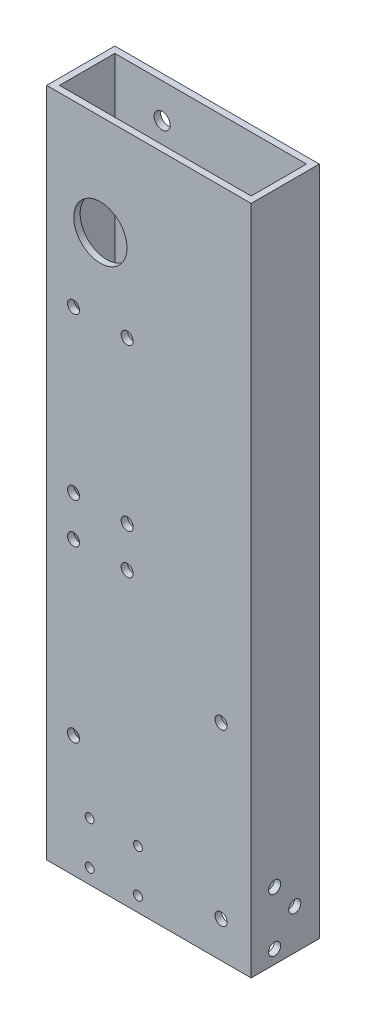
SolidWorks part; units mm, degrees
material "6063-T5"
ref_plane "Front Plane" through (0, 0, 0) normal (0, 0, 1) x (1, 0, 0)
ref_plane "Top Plane" through (0, 0, 0) normal (0, 1, 0) x (1, 0, 0)
ref_plane "Right Plane" through (0, 0, 0) normal (1, 0, 0) x (0, 0, -1)
sketch "Sketch1" plane through (0, 0, 0) normal (0, 1, 0) x (1, 0, 0)
  line L1 (-76.2, 25.4) -> (76.2, 25.4)
  line L2 (-76.2, 25.4) -> (-76.2, -25.4)
  line L3 (-76.2, -25.4) -> (76.2, -25.4)
  line L4 (76.2, 25.4) -> (76.2, -25.4)
  line L5 (-76.2, 25.4) -> (76.2, -25.4) construction
  line L6 (-76.2, -25.4) -> (76.2, 25.4) construction
  point P0 (0, 0)
  dimension "D1" = 152.4
  dimension "D2" = 50.8
extrude "Extrude-Thin1" add sketch "Sketch1" along normal blind 500 thin thin type one direction reverse wall 4.7625
hole_wizard "M8 Clearance Hole1" positions "Sketch3" profile "Sketch4" hole size "M8" standard "ANSI Metric" end condition through all
sketch "Sketch3" plane through (0, 0, 25.4) normal (0, 0, 1) x (1, 0, 0)
  line L0 (-76.2, 227) -> (3.8, 227)
  line L1 (-76.2, 500) -> (-76.2, 0) construction
  line L3 (-76.2, 0) -> (76.2, 0) construction
  line L4 (3.8, 227) -> (3.8, 387)
  line L5 (3.8, 387) -> (-76.2, 387)
  line L6 (-76.2, 387) -> (-76.2, 227)
  line L8 (-56.2, 217) -> (-16.2, 217)
  line L11 (-56.2, 217) -> (-56.2, 153.6667)
  line L12 (-56.2, 153.6667) -> (-56.2, 90.3333)
  line L13 (-56.2, 90.3333) -> (-56.2, 27)
  line L15 (-36.2, 217) -> (-36.2, 227)
  line L17 (-56.2, 27) -> (53.8, 27)
  line L18 (53.8, 27) -> (53.8, 153.6667)
  line L19 (53.8, 153.6667) -> (-56.2, 153.6667)
  line L22 (-56.2, 90.3333) -> (-76.2, 90.3333)
  line L27 (-36.2, 425) -> (-36.2, 387)
  circle A0 centre (-36.2, 425) radius 49.2125
  point P18 (-56.2, 217)
  point P19 (-16.2, 217)
  point P26 (-56.2, 90.3333)
  point P35 (53.8, 27)
  point P36 (53.8, 153.6667)
  dimension "D9" = 98.425
  dimension "D1" = 200
  dimension "D2" = 80
  dimension "D3" = 160
  dimension "D4" = 27
  dimension "D5" = 10
  dimension "D6" = 40
  dimension "D7" = 110
  dimension "D8" = 38
sketch "Sketch4" plane through (53.8, 153.6667, 25.4) normal (1, 0, 0) x (0, -1, 0)
  line L0 (0, 0) -> (0, 50.8)
  line L1 (0, 50.8) -> (4.5, 50.8)
  line L2 (4.5, 50.8) -> (4.5, 0)
  line L5 (4.5, 0) -> (0, 0)
  line L11 (0, -6.35) -> (0, 107.95) construction
  dimension "Thru Hole Dia." = 9
  dimension "Thru Hole Depth" = 50.8
hole_wizard "M8 Clearance Hole2" positions "Sketch5" profile "Sketch6" hole size "M8" standard "ANSI Metric" end condition through all
sketch "Sketch5" plane through (0, 0, 25.4) normal (0, 0, 1) x (1, 0, 0)
  line L1 (-56.2, 367) -> (-16.2, 367)
  line L2 (-56.2, 367) -> (-56.2, 247)
  line L3 (-56.2, 247) -> (-16.2, 247)
  line L4 (-16.2, 367) -> (-16.2, 247)
  line L5 (-56.2, 217) -> (-16.2, 217) construction
  line L6 (-36.2, 227) -> (-36.2, 247)
  line L7 (-76.2, 227) -> (3.8, 227) construction
  point P1 (-56.2, 367)
  point P2 (-16.2, 247)
  point P153 (-56.2, 247)
  point P154 (-16.2, 367)
  dimension "D1" = 20
  dimension "D2" = 120
sketch "Sketch6" plane through (-56.2, 367, 25.4) normal (1, 0, 0) x (0, -1, 0)
  line L0 (0, 0) -> (0, 50.8)
  line L1 (0, 50.8) -> (4.5, 50.8)
  line L2 (4.5, 50.8) -> (4.5, 0)
  line L5 (4.5, 0) -> (0, 0)
  line L11 (0, -6.35) -> (0, 107.95) construction
  dimension "Thru Hole Dia." = 9
  dimension "Thru Hole Depth" = 50.8
hole_wizard "Ø12.0 (12) Diameter Hole1" positions "Sketch7" profile "Sketch8" hole size "Ø12.0" standard "ANSI Metric" end condition up to next
sketch "Sketch7" plane through (0, 0, -25.4) normal (0, 0, -1) x (-1, 0, 0)
  line L0 (-13.0125, 425) -> (36.2, 375.7875)
  line L3 (-13.0125, 425) -> (36.2, 474.2125)
  line L4 (36.2, 474.2125) -> (85.4125, 425)
  line L5 (85.4125, 425) -> (36.2, 375.7875)
  line L7 (36.2, 425) -> (36.2, 387) construction
  circle A0 centre (36.2, 425) radius 49.2125 construction
  point P0 (36.2, 375.7875)
  point P4 (-13.0125, 425)
  point P6 (36.2, 474.2125)
sketch "Sketch8" plane through (-36.2, 375.7875, -25.4) normal (1, 0, 0) x (0, 1, 0)
  line L0 (0, 0) -> (0, 4.7625)
  line L1 (0, 4.7625) -> (6, 4.7625)
  line L2 (6, 4.7625) -> (6, 0)
  line L5 (6, 0) -> (0, 0)
  line L11 (0, -6.35) -> (0, 107.95) construction
  dimension "Thru Hole Dia." = 12
  dimension "Thru Hole Depth" = 4.7625
sketch "Sketch9" plane through (0, 0, 0) normal (0, 0, 1) x (1, 0, 0)
  circle A0 centre (-36.2, 425) radius 19.8438
  dimension "D1" = 39.6875
extrude "Cut-Extrude1" cut sketch "Sketch9" against normal through all and the other way through all
hole_wizard "M6 Clearance Hole1" positions "Sketch10" profile "Sketch11" hole size "M6" standard "ANSI Metric" end condition through all
sketch "Sketch10" plane through (0, 0, 25.4) normal (0, 0, 1) x (1, 0, 0)
  line L1 (-8.2, 43) -> (-44.2, 43)
  line L2 (-8.2, 43) -> (-8.2, 11)
  line L3 (-8.2, 11) -> (-44.2, 11)
  line L4 (-44.2, 43) -> (-44.2, 11)
  line L5 (-8.2, 43) -> (-44.2, 11) construction
  line L6 (-8.2, 11) -> (-44.2, 43) construction
  line L8 (-56.2, 27) -> (53.8, 27) construction
  line L9 (-76.2, 500) -> (-76.2, 0) construction
  point P2 (-44.2, 11)
  point P107 (-8.2, 43)
  point P108 (-8.2, 11)
  point P109 (-44.2, 43)
  point P114 (-26.2, 27)
  dimension "D1" = 36
  dimension "D2" = 32
  dimension "D3" = 50
sketch "Sketch11" plane through (-44.2, 11, 25.4) normal (1, 0, 0) x (0, -1, 0)
  line L0 (0, 0) -> (0, 50.8)
  line L1 (0, 50.8) -> (3.3, 50.8)
  line L2 (3.3, 50.8) -> (3.3, 0)
  line L5 (3.3, 0) -> (0, 0)
  line L11 (0, -6.35) -> (0, 107.95) construction
  dimension "Thru Hole Dia." = 6.6
  dimension "Thru Hole Depth" = 50.8
hole_wizard "M8 Clearance Hole3" positions "Sketch12" profile "Sketch14" hole size "M8" standard "ANSI Metric" end condition up to next
sketch "Sketch12" plane through (76.2, 0, 0) normal (1, 0, 0) x (0, 0, -1)
  line L1 (-7.9, 50) -> (7.1, 50)
  line L2 (-7.9, 50) -> (-7.9, 10)
  line L3 (-7.9, 10) -> (7.1, 10)
  line L4 (7.1, 50) -> (7.1, 10)
  line L5 (-25.4, 0) -> (25.4, 0) construction
  line L6 (-25.4, 90.3333) -> (-25.4, 27) construction
  point P1 (-7.9, 50)
  point P87 (-7.9, 10)
  point P98 (7.1, 30)
  dimension "D1" = 10
  dimension "D2" = 17.5
  dimension "D3" = 15
  dimension "D4" = 40
sketch "Sketch14" plane through (76.2, 50, 7.9) normal (0, 1, 0) x (0, 0, -1)
  line L0 (0, 0) -> (0, 4.7625)
  line L1 (0, 4.7625) -> (4.5, 4.7625)
  line L2 (4.5, 4.7625) -> (4.5, 0)
  line L5 (4.5, 0) -> (0, 0)
  line L11 (0, -6.35) -> (0, 107.95) construction
  dimension "Thru Hole Dia." = 9
  dimension "Thru Hole Depth" = 4.7625
hole_wizard "Ø16.0 (16) Diameter Hole1" positions "Sketch15" profile "Sketch16" hole size "Ø16.0" standard "ANSI Metric" end condition up to next
sketch "Sketch15" plane through (-76.2, 0, 0) normal (-1, 0, 0) x (0, 0, 1)
  line L0 (-7.1, 50) -> (7.9, 10)
  point P0 (0.4, 30)
sketch "Sketch16" plane through (-76.2, 30, 0.4) normal (0, 1, 0) x (0, 0, 1)
  line L0 (0, 0) -> (0, 4.7625)
  line L1 (0, 4.7625) -> (8, 4.7625)
  line L2 (8, 4.7625) -> (8, 0)
  line L5 (8, 0) -> (0, 0)
  line L11 (0, -6.35) -> (0, 107.95) construction
  dimension "Thru Hole Dia." = 16
  dimension "Thru Hole Depth" = 4.7625
